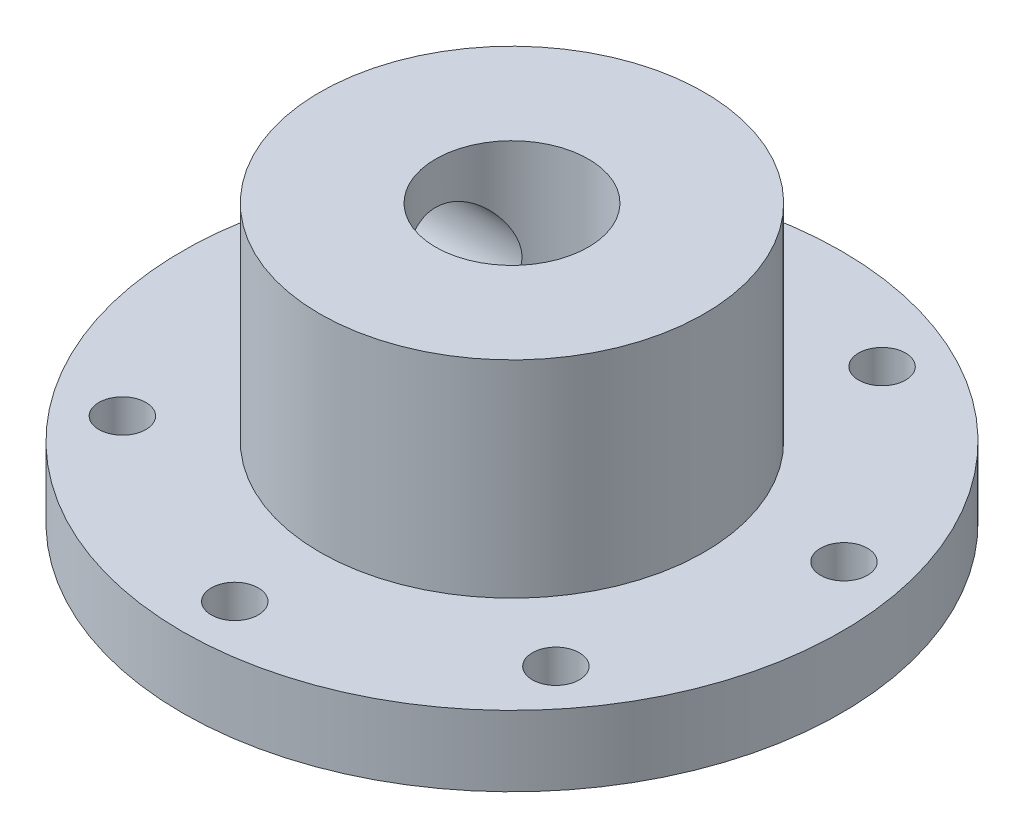
SolidWorks part; units mm, degrees
ref_plane "Front Plane" through (0, 0, 0) normal (0, 0, 1) x (1, 0, 0)
ref_plane "Top Plane" through (0, 0, 0) normal (0, 1, 0) x (1, 0, 0)
ref_plane "Right Plane" through (0, 0, 0) normal (1, 0, 0) x (0, 0, -1)
sketch "Sketch1" plane through (0, 0, 0) normal (0, 1, 0) x (1, 0, 0)
  circle A0 centre (0, 0) radius 3.25
  circle A1 centre (0, 0) radius 8.175
  circle A2 centre (0, 0) radius 14.0236
  point P25 (0, 0)
extrude "Boss-Extrude1" add sketch "Sketch1" along normal blind 8.7807 and the other way blind 3 contours A1 A0 region at (-7.9438, 0, 0)
extrude "Boss-Extrude2" add sketch "Sketch1<3>" against normal blind 3 separate body contours A2 A1 region at (-13.627, 0, 0)
sketch "Sketch1<3>" plane through (0, 0, 0) normal (0, 1, 0) x (1, 0, 0) same geometry as "Sketch1"
sketch "Sketch2" plane through (0, 0, 0) normal (1, 0, 0) x (0, 0, -1)
  line L0 (0, 2) -> (0, 0)
  circle A0 centre (0, 4.5) radius 2.5
  dimension "D1" = 2
  dimension "D2" = 2
extrude "Cut-Extrude1" cut sketch "Sketch2" against normal blind 15 contours A0
sketch "Sketch3" plane through (0, -3, 0) normal (0, -1, 0) x (1, 0, 0)
  circle A1 centre (0, 11.7973) radius 1
  circle A2 centre (9.2235, 7.3555) radius 1
  circle A3 centre (11.5015, -2.6252) radius 1
  circle A4 centre (5.1187, -10.629) radius 1
  circle A5 centre (-5.1187, -10.629) radius 1
  circle A6 centre (-11.5015, -2.6252) radius 1
  circle A7 centre (-9.2235, 7.3555) radius 1
  point P2 (-12.4894, 10.1484)
  point P3 (0, 0)
  point P14 (0, 0)
  point P18 (0, 11.7973)
  dimension "D1" = 7
extrude "Cut-Extrude2" cut sketch "Sketch3" against normal through all and the other way blind 3.175
sketch "Sketch4" plane through (0, -3, 0) normal (0, -1, 0) x (1, 0, 0)
  circle A0 centre (0, 0) radius 4.175
extrude "Boss-Extrude4" add sketch "Sketch4" along normal blind 5 contours A0
extrude "Cut-Extrude3" cut sketch "Sketch1<5>" against normal blind 13 and the other way blind 15 contours A0
sketch "Sketch1<5>" plane through (0, 0, 0) normal (0, 1, 0) x (1, 0, 0) same geometry as "Sketch1"
